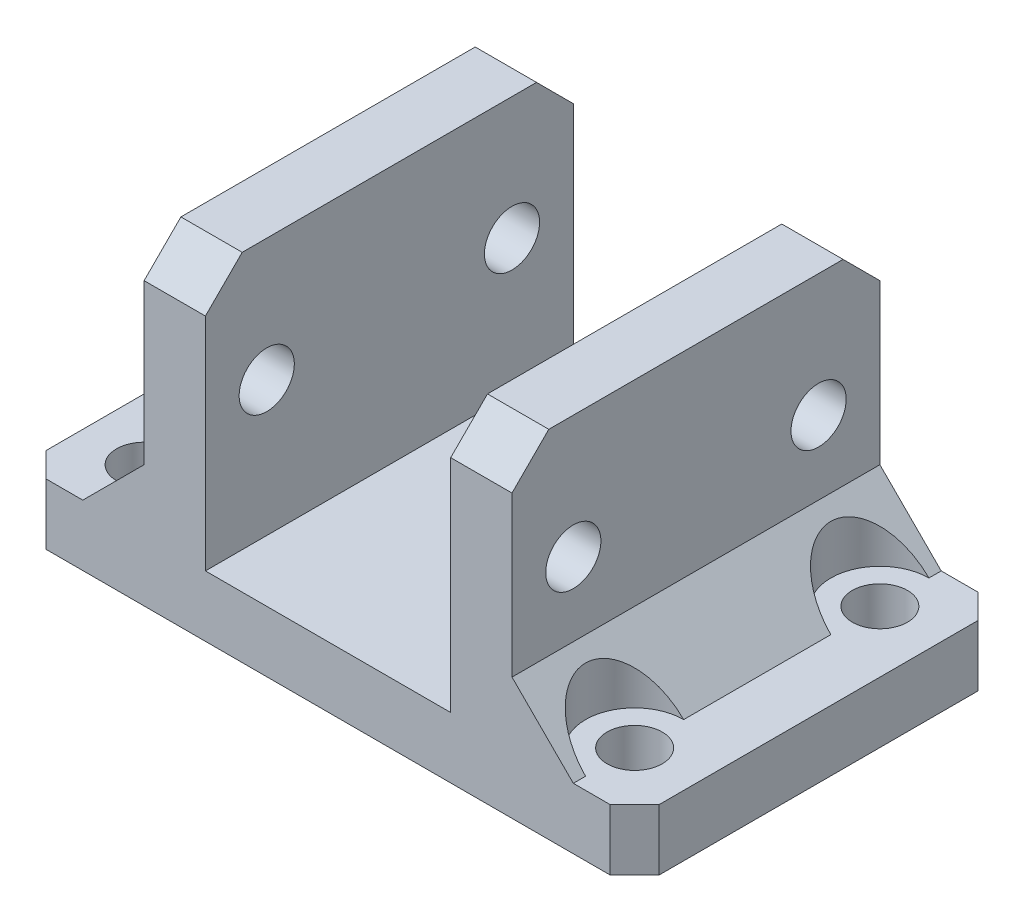
SolidWorks part; units mm, degrees
ref_plane "Front Plane" through (0, 0, 0) normal (0, 0, 1) x (1, 0, 0)
ref_plane "Top Plane" through (0, 0, 0) normal (0, 1, 0) x (1, 0, 0)
ref_plane "Right Plane" through (0, 0, 0) normal (1, 0, 0) x (0, 0, -1)
sketch "Sketch13" plane through (0, 0, 0) normal (0, 0, 1) x (1, 0, 0)
  line L2 (-10, 10) -> (-10, -11)
  line L3 (-10, -11) -> (10, -11)
  line L4 (10, 10) -> (10, -11)
  line L5 (-15, -11) -> (-25, -11)
  line L7 (10, -11) -> (-10, -11)
  line L8 (15, -11) -> (15, 10)
  line L9 (15, 10) -> (10, 10)
  line L10 (-15, -11) -> (-15, 10)
  line L13 (-10, 10) -> (-15, 10)
  line L14 (25, -15.9758) -> (-25, -15.9758)
  line L15 (25, -15.9758) -> (25, -11)
  line L16 (25, -11) -> (15, -11)
  line L17 (-25, -15.9758) -> (-25, -11)
  line L22 (10, -11) -> (-10, -11)
  point P0 (0, 0)
  point P6 (0, 0)
  point P13 (0, -12.4879)
  dimension "D1" = 20
  dimension "D2" = 21
  dimension "D3" = 10
  dimension "D4" = 5
  dimension "D5" = 5
  dimension "D6" = 10
extrude "Boss-Extrude1" add sketch "Sketch13" against normal blind 30 contours L17 L14 L15 L16 L8 L9 L4 L3 L2 L13 L10 L5 region at (-10.5634, -0.5, 0)
sketch "Sketch14" plane through (0, -11, 0) normal (0, 1, 0) x (1, 0, 0)
  line L0 (15, 30) -> (25, 30)
  line L2 (25, 0) -> (15, 0) construction
  line L3 (15, 0) -> (25, 0)
  line L4 (25, 30) -> (25, 0) construction
  line L6 (20, 30) -> (20, 0)
  line L10 (-25, 30) -> (-25, 0) construction
  circle A0 centre (20, 25) radius 2.25
  circle A1 centre (20, 5) radius 2.25
  circle A2 centre (-20, 5) radius 2.25
  circle A3 centre (-20, 25) radius 2.25
  circle A4 centre (20, 25) radius 4
  circle A5 centre (20, 5) radius 4
  circle A6 centre (-20, 5) radius 4
  circle A7 centre (-20, 25) radius 4
  dimension "D1" = 5
  dimension "D3" = 5
  dimension "D2" = 5
  dimension "D4" = 5
  dimension "D5" = 5
  dimension "D8" = 5
sketch "Sketch15" plane through (15, 0, 0) normal (1, 0, 0) x (0, 0, -1)
  line L0 (0, 0) -> (30, 0) construction
  line L1 (30, -11) -> (30, 10) construction
  line L2 (0, -11) -> (0, 10) construction
  circle A0 centre (5, 0) radius 2.25
  circle A1 centre (25, 0) radius 2.25
  dimension "D1" = 5
  dimension "D2" = 5
extrude "Cut-Extrude1" cut sketch "Sketch15" against normal blind 31
extrude "Cut-Extrude2" cut sketch "Sketch14" against normal blind 5 contours A3 | A2 | A0 | A0 | A1 | A1 region at (20.9549, -11, -25) region at (19.0451, -11, -25) region at (20.9549, -11, -5) region at (19.0451, -11, -5) region at (-20, -11, -5) region at (-20, -11, -25)
chamfer "Chamfer2" distance 3 angle 45 4 edges at (-12.5, 10, 0) (12.5, 10, 0) (-12.5, 10, -30) (12.5, 10, -30)
chamfer "Chamfer3" distance 2 angle 45 4 edges at (25, -13.4879, -30) (25, -13.4879, 0) (-25, -13.4879, 0) (-25, -13.4879, -30)
sketch "Sketch20" plane through (0, -15.9758, 0) normal (0, -1, 0) x (1, 0, 0)
  line L1 (-20, -5) -> (20, -5)
  line L2 (-20, -5) -> (-20, -25)
  line L3 (-20, -25) -> (20, -25)
  line L4 (20, -5) -> (20, -25)
chamfer "Chamfer4" distance 5 angle 45 2 edges at (-15, -11, -15) (15, -11, -15)
extrude "Cut-Extrude3" cut sketch "Sketch14<7>" along normal blind 10 contours A7 A3 | A6 A2 | L6 A5 A1 | L6 A4 A0 | L6 A4 A0 | L6 A5 A1 region at (22.7652, -11, -27.7652) region at (22.7652, -11, -7.7652) region at (19.9106, -11, -8.125) region at (19.9106, -11, -28.125) region at (-23.8869, -11, -5) region at (-23.8869, -11, -25)
sketch "Sketch14<7>" plane through (0, -11, 0) normal (0, 1, 0) x (1, 0, 0) same geometry as "Sketch14"
